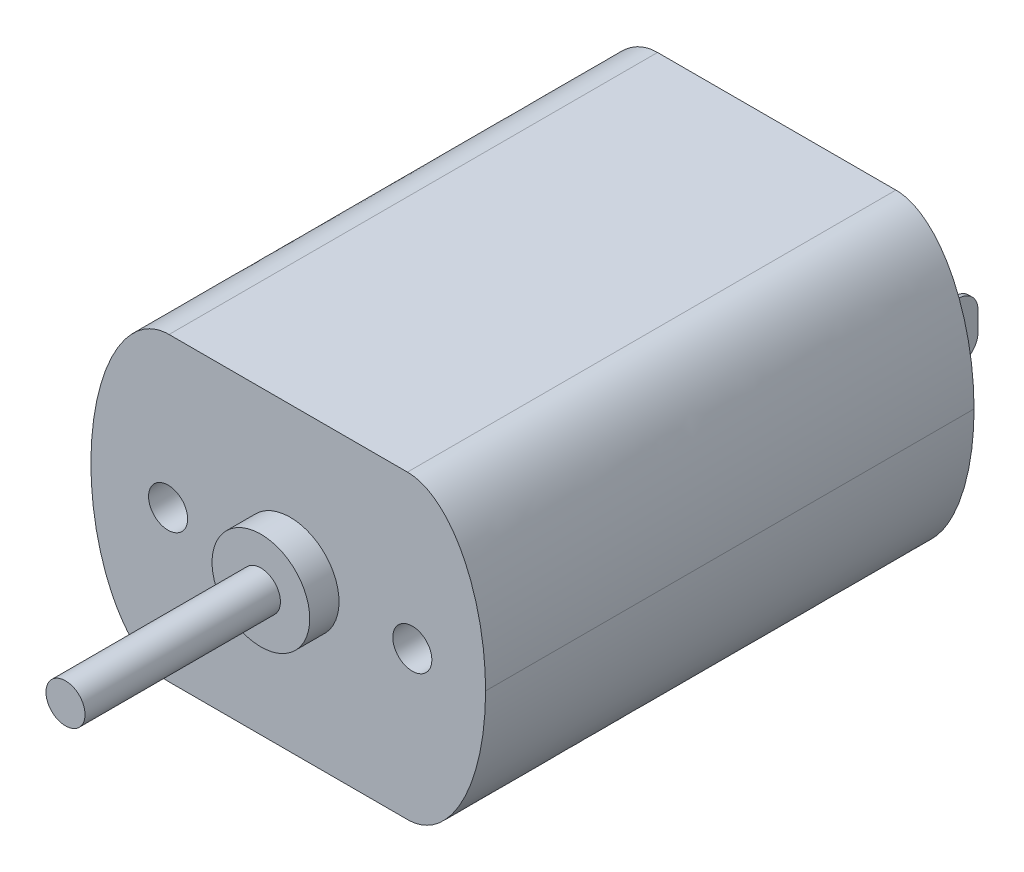
SolidWorks part; units mm, degrees
material "AISI 304"
ref_plane "前视基准面" through (0, 0, 0) normal (0, 0, 1) x (1, 0, 0)
ref_plane "上视基准面" through (0, 0, 0) normal (0, 1, 0) x (1, 0, 0)
ref_plane "右视基准面" through (0, 0, 0) normal (1, 0, 0) x (0, 0, -1)
sketch "草图1" plane through (0, 0, 0) normal (0, 0, 1) x (1, 0, 0)
  line L1 (0, 0) -> (20.2, 0)
  line L2 (0, 0) -> (0, -15.4)
  line L3 (0, -15.4) -> (20.2, -15.4)
  line L4 (20.2, 0) -> (20.2, -15.4)
  dimension "D1" = 20.2
  dimension "D2" = 15.4
extrude "凸台-拉伸1" add sketch "草图1" along normal blind 25
sketch "草图2" plane through (0, 0, 25) normal (0, 0, 1) x (1, 0, 0)
  line L0 (20.2, 0) -> (0, 0) construction
  line L1 (20.2, -15.4) -> (20.2, 0) construction
  circle A0 centre (10.2, -7.5) radius 2.5
  dimension "D3" = 5
  dimension "D1" = 7.5
  dimension "D2" = 10
extrude "凸台-拉伸2" add sketch "草图2" along normal blind 1.5
sketch "草图3" plane through (0, 0, 26.5) normal (0, 0, 1) x (1, 0, 0)
  circle A0 centre (10.2, -7.5) radius 1
  dimension "D1" = 2
extrude "凸台-拉伸3" add sketch "草图3" along normal blind 10
fillet "圆角2" radius 4 2 edges at (20.2, -15.4, 12.5) (0, 0, 12.5) second distance 7.7 first distance on face at (10.1, -15.4, 12.5) first distance on face at (10.1, 0, 12.5)
fillet "圆角3" radius 7.7 2 edges at (20.2, 0, 12.5) (0, -15.4, 12.5) second distance 4 first distance on face at (20.2, -5.775, 15.625) first distance on face at (0, -9.625, 15.625)
sketch "草图4" plane through (0, 0, 25) normal (0, 0, 1) x (1, 0, 0)
  line L0 (4, -15.4) -> (16.2, -15.4) construction
  circle A0 centre (3.95, -7.7) radius 1
  circle A1 centre (16.45, -7.7) radius 1
  circle A3 centre (10.2, -7.5) radius 2.5 construction
  dimension "D1" = 2
  dimension "D2" = 2
  dimension "D3" = 12.5
  dimension "D4" = 7.7
  dimension "D5" = 6.25
extrude "切除-拉伸1" cut sketch "草图4" against normal blind 5
sketch "草图5" plane through (0, 0, 0) normal (0, 0, -1) x (-1, 0, 0)
  line L0 (-4, -15.4) -> (-16.2, -15.4) construction
  circle A0 centre (-10.1, -7.7) radius 2.5
  point P4 (-10.1, -15.4)
  point P6 (-19.1119, -7.5558)
  point P7 (-10.2088, -13.952)
  dimension "D1" = 5
  dimension "D2" = 7.7
  dimension "D3" = 0
extrude "凸台-拉伸4" add sketch "草图5" along normal blind 1.5
sketch "草图6" plane through (0, 0, 0) normal (0, 0, -1) x (-1, 0, 0)
  line L0 (-16.2, 0) -> (-4, 0) construction
  line L1 (-3.4364, -6.2) -> (-3.6364, -6.2)
  line L2 (-3.4364, -6.2) -> (-3.4364, -9.2)
  line L3 (-3.4364, -9.2) -> (-3.6364, -9.2)
  line L4 (-3.6364, -6.2) -> (-3.6364, -9.2)
  line L5 (-16.2024, -6.2) -> (-16.4024, -6.2)
  line L6 (-16.2024, -6.2) -> (-16.2024, -9.2)
  line L7 (-16.2024, -9.2) -> (-16.4024, -9.2)
  line L8 (-16.4024, -6.2) -> (-16.4024, -9.2)
  dimension "D1" = 3
  dimension "D2" = 0.2
  dimension "D3" = 3
  dimension "D4" = 0.2
  dimension "D5" = 6.2
  dimension "D6" = 6.2
extrude "凸台-拉伸5" add sketch "草图6" along normal blind 4
fillet "圆角4" radius 1 4 edges at (3.5364, -9.2, -4) (16.3024, -9.2, -4) (16.3024, -6.2, -4) (3.5364, -6.2, -4)
sketch "草图7" plane through (3.4364, 0, 0) normal (-1, 0, 0) x (0, 0, 1)
  line L0 (-3, -9.2) -> (0, -9.2) construction
  line L1 (-4, -8.2) -> (-4, -7.2) construction
  circle A0 centre (-3, -7.7) radius 0.3
  dimension "D1" = 0.6
  dimension "D2" = 1.5
  dimension "D3" = 1
extrude "切除-拉伸2" cut sketch "草图7" against normal through all
